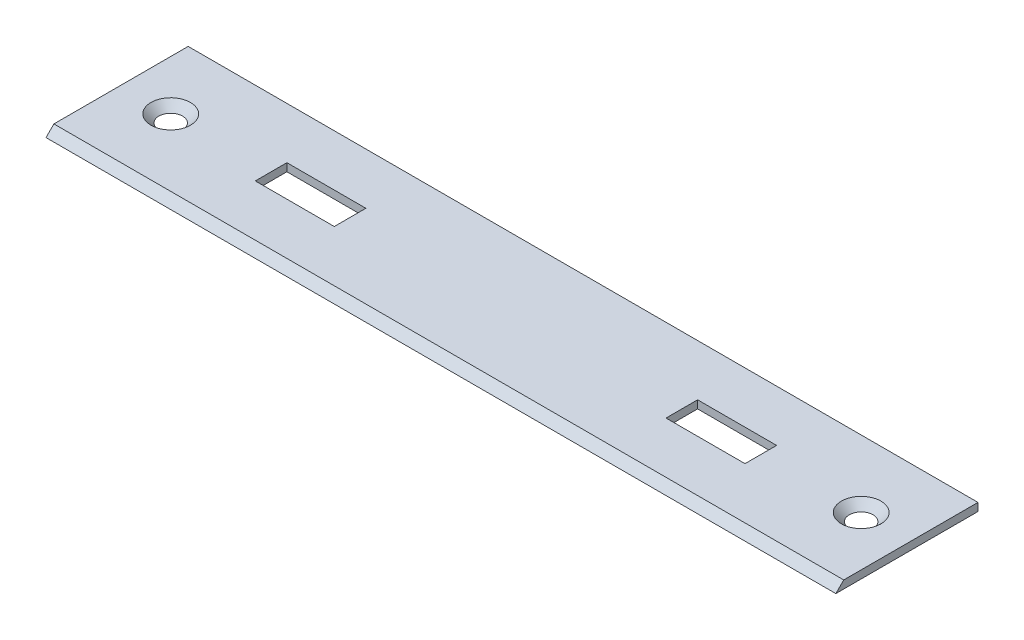
SolidWorks part; units mm, degrees
ref_plane "Спереди" through (0, 0, 0) normal (0, 0, 1) x (1, 0, 0)
ref_plane "Сверху" through (0, 0, 0) normal (0, 1, 0) x (1, 0, 0)
ref_plane "Справа" through (0, 0, 0) normal (1, 0, 0) x (0, 0, -1)
sketch "Эскиз1" plane through (0, 0, 0) normal (0, 1, 0) x (1, 0, 0)
  line L1 (-50, -9) -> (50, -9)
  line L2 (-50, -9) -> (-50, 9)
  line L3 (-50, 9) -> (50, 9)
  line L4 (50, -9) -> (50, 9)
  line L5 (-50, -9) -> (50, 9) construction
  line L6 (-50, 9) -> (50, -9) construction
  point P0 (0, 0)
  dimension "D1" = 100
  dimension "D2" = 18
extrude "Бобышка-Вытянуть1" add sketch "Эскиз1" along normal blind 1
chamfer "Фаска1" distance 1 angle 45 1 edges at (0, 1, 9)
sketch "Эскиз2" plane through (0, 1, 0) normal (0, 1, 0) x (1, 0, 0)
  line L0 (-50, 0.5) -> (50, 0.5) construction
  line L1 (-50, 9) -> (-50, -8) construction
  line L2 (50, -8) -> (50, 9) construction
  line L4 (-31, 2.5) -> (-21, 2.5)
  line L5 (-31, 2.5) -> (-31, -1.5)
  line L6 (-31, -1.5) -> (-21, -1.5)
  line L7 (-21, 2.5) -> (-21, -1.5)
  line L8 (-31, 2.5) -> (-21, -1.5) construction
  line L9 (-31, -1.5) -> (-21, 2.5) construction
  line L10 (21, 2.5) -> (31, 2.5)
  line L11 (21, 2.5) -> (21, -1.5)
  line L12 (21, -1.5) -> (31, -1.5)
  line L13 (31, 2.5) -> (31, -1.5)
  line L14 (21, 2.5) -> (31, -1.5) construction
  line L15 (21, -1.5) -> (31, 2.5) construction
  point P6 (-26, 0.5)
  point P11 (26, 0.5)
  dimension "D1" = 21
  dimension "D2" = 42
  dimension "D3" = 4
  dimension "D4" = 4
  dimension "D5" = 10
  dimension "D6" = 10
extrude "Вырез-Вытянуть1" cut sketch "Эскиз2" against normal blind 1
sketch "Эскиз3" plane through (0, 1, 0) normal (0, 1, 0) x (1, 0, 0)
  line L0 (-50, 0.5) -> (50, 0.5) construction
  line L1 (-50, 9) -> (-50, -8) construction
  line L2 (50, -8) -> (50, 9) construction
  line L3 (0, 9) -> (0, -8) construction
  line L4 (50, 9) -> (-50, 9) construction
  line L5 (-50, -8) -> (50, -8) construction
  circle A0 centre (-43.7097, 0.5) radius 1.5
  circle A1 centre (43.7097, 0.5) radius 1.5
extrude "Вырез-Вытянуть2" cut sketch "Эскиз3" against normal blind 20
chamfer "Фаска2" distance 1 angle 45 2 edges at (43.7097, 1, -2) (-43.7097, 1, 1)
